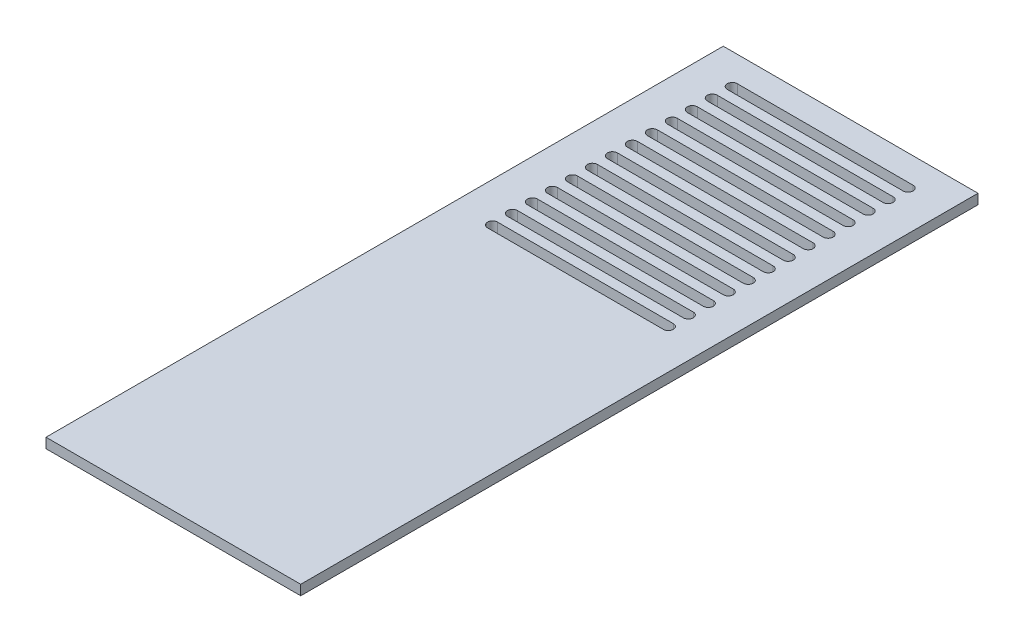
SolidWorks part; units mm, degrees
ref_plane "Front Plane" through (0, 0, 0) normal (0, 0, 1) x (1, 0, 0)
ref_plane "Top Plane" through (0, 0, 0) normal (0, 1, 0) x (1, 0, 0)
ref_plane "Right Plane" through (0, 0, 0) normal (1, 0, 0) x (0, 0, -1)
sketch "Sketch1" plane through (0, 0, 0) normal (0, 1, 0) x (1, 0, 0)
  line L1 (-56, 63.4545) -> (-5, 63.4545)
  line L2 (-56, 63.4545) -> (-56, -72.5455)
  line L3 (-56, -72.5455) -> (-5, -72.5455)
  line L4 (-5, 63.4545) -> (-5, -72.5455)
  dimension "D1" = 136
  dimension "D2" = 51
extrude "Boss-Extrude1" add sketch "Sketch1" along normal blind 2
sketch "Sketch3" plane through (0, 2, 0) normal (0, 1, 0) x (1, 0, 0)
  line L0 (-5, 63.4545) -> (-56, 63.4545) construction
  line L1 (-49.1, 58.3545) -> (-11.9, 58.3545)
  line L2 (-49.1, 58.3545) -> (-49.1, 8.4545)
  line L3 (-49.1, 8.4545) -> (-11.9, 8.4545)
  line L4 (-11.9, 58.3545) -> (-11.9, 8.4545)
  dimension "D1" = 5.1
  dimension "D2" = 37.2
  dimension "D4" = 49.9
sketch "Sketch4" plane through (0, 2, 0) normal (0, 1, 0) x (1, 0, 0)
  line L0 (-48.1, 57.3545) -> (-12.9, 57.3545) construction
  line L1 (-48.1, 58.3545) -> (-12.9, 58.3545)
  line L2 (-48.1, 56.3545) -> (-12.9, 56.3545)
  line L3 (-49.1, 58.3545) -> (-49.1, 8.4545) construction
  line L4 (-49.1, 58.3545) -> (-11.9, 58.3545) construction
  line L5 (-48.1, 53.3545) -> (-12.9, 53.3545) construction
  line L6 (-48.1, 54.3545) -> (-12.9, 54.3545)
  line L7 (-48.1, 52.3545) -> (-12.9, 52.3545)
  line L8 (-48.1, 49.3545) -> (-12.9, 49.3545) construction
  line L9 (-48.1, 50.3545) -> (-12.9, 50.3545)
  line L10 (-48.1, 48.3545) -> (-12.9, 48.3545)
  line L11 (-48.1, 45.3545) -> (-12.9, 45.3545) construction
  line L12 (-48.1, 46.3545) -> (-12.9, 46.3545)
  line L13 (-48.1, 44.3545) -> (-12.9, 44.3545)
  line L14 (-48.1, 41.3545) -> (-12.9, 41.3545) construction
  line L15 (-48.1, 42.3545) -> (-12.9, 42.3545)
  line L16 (-48.1, 40.3545) -> (-12.9, 40.3545)
  line L17 (-48.1, 37.3545) -> (-12.9, 37.3545) construction
  line L18 (-48.1, 38.3545) -> (-12.9, 38.3545)
  line L19 (-48.1, 36.3545) -> (-12.9, 36.3545)
  line L20 (-48.1, 33.3545) -> (-12.9, 33.3545) construction
  line L21 (-48.1, 34.3545) -> (-12.9, 34.3545)
  line L22 (-48.1, 32.3545) -> (-12.9, 32.3545)
  line L23 (-48.1, 29.3545) -> (-12.9, 29.3545) construction
  line L24 (-48.1, 30.3545) -> (-12.9, 30.3545)
  line L25 (-48.1, 28.3545) -> (-12.9, 28.3545)
  line L26 (-48.1, 25.3545) -> (-12.9, 25.3545) construction
  line L27 (-48.1, 26.3545) -> (-12.9, 26.3545)
  line L28 (-48.1, 24.3545) -> (-12.9, 24.3545)
  line L29 (-48.1, 21.3545) -> (-12.9, 21.3545) construction
  line L30 (-48.1, 22.3545) -> (-12.9, 22.3545)
  line L31 (-48.1, 20.3545) -> (-12.9, 20.3545)
  line L32 (-48.1, 17.3545) -> (-12.9, 17.3545) construction
  line L33 (-48.1, 18.3545) -> (-12.9, 18.3545)
  line L34 (-48.1, 16.3545) -> (-12.9, 16.3545)
  line L35 (-48.1, 13.3545) -> (-12.9, 13.3545) construction
  line L36 (-48.1, 14.3545) -> (-12.9, 14.3545)
  line L37 (-48.1, 12.3545) -> (-12.9, 12.3545)
  line L38 (-48.1, 9.3545) -> (-12.9, 9.3545) construction
  line L39 (-48.1, 10.3545) -> (-12.9, 10.3545)
  line L40 (-48.1, 8.3545) -> (-12.9, 8.3545)
  arc A0 (-48.1, 58.3545) -> (-48.1, 56.3545) centre (-48.1, 57.3545) ccw
  arc A1 (-12.9, 56.3545) -> (-12.9, 58.3545) centre (-12.9, 57.3545) ccw
  arc A2 (-48.1, 54.3545) -> (-48.1, 52.3545) centre (-48.1, 53.3545) ccw
  arc A3 (-12.9, 52.3545) -> (-12.9, 54.3545) centre (-12.9, 53.3545) ccw
  arc A4 (-48.1, 50.3545) -> (-48.1, 48.3545) centre (-48.1, 49.3545) ccw
  arc A5 (-12.9, 48.3545) -> (-12.9, 50.3545) centre (-12.9, 49.3545) ccw
  arc A6 (-48.1, 46.3545) -> (-48.1, 44.3545) centre (-48.1, 45.3545) ccw
  arc A7 (-12.9, 44.3545) -> (-12.9, 46.3545) centre (-12.9, 45.3545) ccw
  arc A8 (-48.1, 42.3545) -> (-48.1, 40.3545) centre (-48.1, 41.3545) ccw
  arc A9 (-12.9, 40.3545) -> (-12.9, 42.3545) centre (-12.9, 41.3545) ccw
  arc A10 (-48.1, 38.3545) -> (-48.1, 36.3545) centre (-48.1, 37.3545) ccw
  arc A11 (-12.9, 36.3545) -> (-12.9, 38.3545) centre (-12.9, 37.3545) ccw
  arc A12 (-48.1, 34.3545) -> (-48.1, 32.3545) centre (-48.1, 33.3545) ccw
  arc A13 (-12.9, 32.3545) -> (-12.9, 34.3545) centre (-12.9, 33.3545) ccw
  arc A14 (-48.1, 30.3545) -> (-48.1, 28.3545) centre (-48.1, 29.3545) ccw
  arc A15 (-12.9, 28.3545) -> (-12.9, 30.3545) centre (-12.9, 29.3545) ccw
  arc A16 (-48.1, 26.3545) -> (-48.1, 24.3545) centre (-48.1, 25.3545) ccw
  arc A17 (-12.9, 24.3545) -> (-12.9, 26.3545) centre (-12.9, 25.3545) ccw
  arc A18 (-48.1, 22.3545) -> (-48.1, 20.3545) centre (-48.1, 21.3545) ccw
  arc A19 (-12.9, 20.3545) -> (-12.9, 22.3545) centre (-12.9, 21.3545) ccw
  arc A20 (-48.1, 18.3545) -> (-48.1, 16.3545) centre (-48.1, 17.3545) ccw
  arc A21 (-12.9, 16.3545) -> (-12.9, 18.3545) centre (-12.9, 17.3545) ccw
  arc A22 (-48.1, 14.3545) -> (-48.1, 12.3545) centre (-48.1, 13.3545) ccw
  arc A23 (-12.9, 12.3545) -> (-12.9, 14.3545) centre (-12.9, 13.3545) ccw
  arc A24 (-48.1, 10.3545) -> (-48.1, 8.3545) centre (-48.1, 9.3545) ccw
  arc A25 (-12.9, 8.3545) -> (-12.9, 10.3545) centre (-12.9, 9.3545) ccw
  point P2 (-30.5, 57.3545)
  point P7 (-49.1, 57.3545)
  point P16 (-30.5, 53.3545)
  point P23 (-30.5, 49.3545)
  point P30 (-30.5, 45.3545)
  point P37 (-30.5, 41.3545)
  point P44 (-30.5, 37.3545)
  point P51 (-30.5, 33.3545)
  point P58 (-30.5, 29.3545)
  point P65 (-30.5, 25.3545)
  point P72 (-30.5, 21.3545)
  point P79 (-30.5, 17.3545)
  point P86 (-30.5, 13.3545)
  point P93 (-30.5, 9.3545)
  dimension "D1" = 0
  dimension "D3" = 13
  dimension "D2" = 0
extrude "Cut-Extrude1" cut sketch "Sketch4" against normal blind 10
sketch "Sketch5" plane through (0, 0, -63.4545) normal (0, 0, -1) x (-1, 0, 0)
  line L1 (56, 2) -> (57, 2)
  line L2 (56, 2) -> (56, 0)
  line L3 (56, 0) -> (57, 0)
  line L4 (57, 2) -> (57, 0)
  line L5 (5, 2) -> (4, 2)
  line L6 (5, 2) -> (5, 0)
  line L7 (5, 0) -> (4, 0)
  line L8 (4, 2) -> (4, 0)
  point P10 (57, 1)
  dimension "D1" = 1
  dimension "D2" = 1
extrude "Boss-Extrude2" add sketch "Sketch5" against normal up to surface (136 mm away) up to face at (-30.5, 1, 72.5455)
sketch "Sketch6" plane through (0, 0, -63.4545) normal (0, 0, -1) x (-1, 0, 0)
  line L1 (57, 0) -> (58, 0)
  line L2 (57, 0) -> (57, 2)
  line L3 (57, 2) -> (58, 2)
  line L4 (58, 0) -> (58, 2)
  line L5 (4, 0) -> (3, 0)
  line L6 (4, 0) -> (4, 2)
  line L7 (4, 2) -> (3, 2)
  line L8 (3, 0) -> (3, 2)
  dimension "D1" = 1
  dimension "D2" = 1
extrude "Boss-Extrude3" add sketch "Sketch6" against normal up to surface (136 mm away) up to face at (-30.5, 1, 72.5455)
sketch "Sketch7" plane through (0, 0, 72.5455) normal (0, 0, 1) x (1, 0, 0)
  line L1 (-66.7377, 9.812) -> (2.0582, 9.812)
  line L2 (-66.7377, 9.812) -> (-66.7377, -16.6136)
  line L3 (-66.7377, -16.6136) -> (2.0582, -16.6136)
  line L4 (2.0582, 9.812) -> (2.0582, -16.6136)
extrude "Cut-Extrude2" cut sketch "Sketch7" against normal blind 0.4
sketch "Sketch8" plane through (0, 0, -63.4545) normal (0, 0, -1) x (-1, 0, 0)
  line L0 (3, 0) -> (58, 0) construction
  line L1 (3, 2) -> (5, 2)
  line L2 (3, 2) -> (3, 0)
  line L3 (3, 0) -> (5, 0)
  line L4 (5, 2) -> (5, 0)
  line L6 (58, 2) -> (56, 2)
  line L7 (58, 2) -> (58, 0)
  line L8 (58, 0) -> (56, 0)
  line L9 (56, 2) -> (56, 0)
  dimension "D1" = 2
  dimension "D2" = 2
extrude "Cut-Extrude3" cut sketch "Sketch8" against normal blind 135.6
